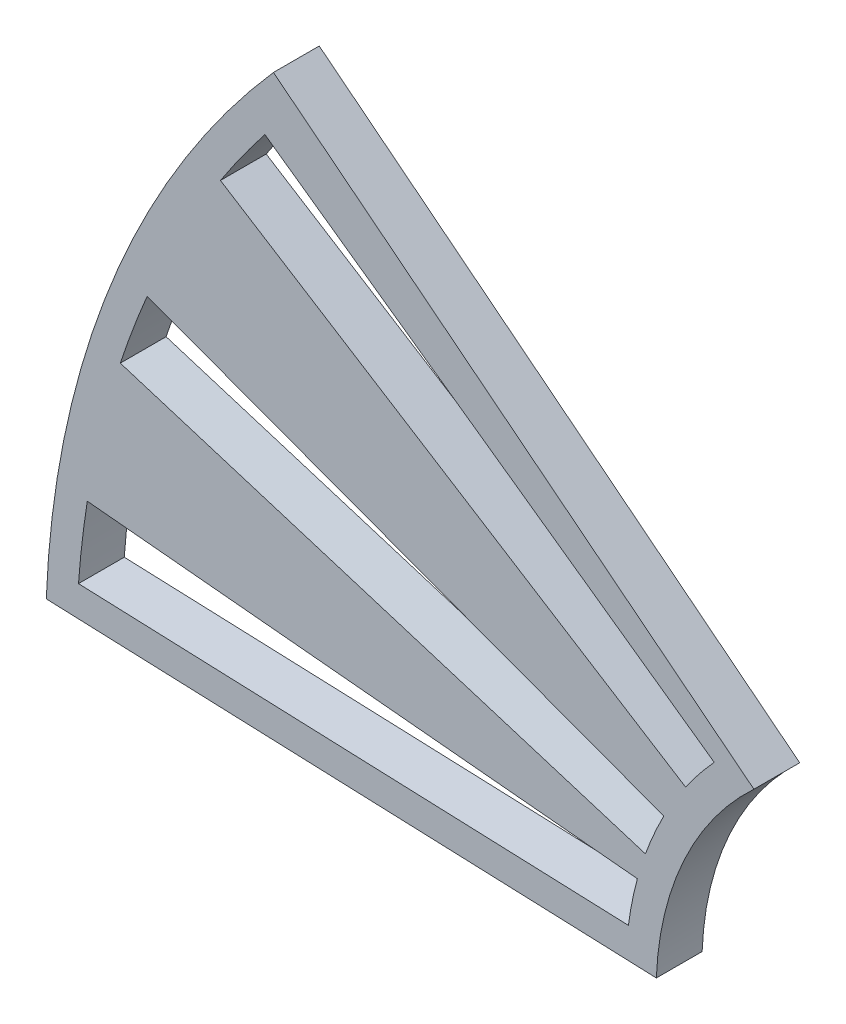
SolidWorks part; units mm, degrees
ref_plane "Front Plane" through (0, 0, 0) normal (0, 0, 1) x (1, 0, 0)
ref_plane "Top Plane" through (0, 0, 0) normal (0, 1, 0) x (1, 0, 0)
ref_plane "Right Plane" through (0, 0, 0) normal (1, 0, 0) x (0, 0, -1)
sketch "Sketch1" plane through (0, 0, 0) normal (0, 0, 1) x (1, 0, 0)
  line L0 (-19.9854, 0.7628) -> (-59.9563, 2.2884)
  line L1 (-16.3569, 14.7123) -> (-16.1915, 14.8941)
  line L2 (0, 0) -> (-50.7795, 31.96) construction
  line L3 (0, 0) -> (-57.3211, 17.7283) construction
  line L4 (-21.8167, 2.8342) -> (-57.8471, 4.2094)
  line L5 (-13.5925, 14.6712) -> (-45.0737, 39.6026)
  line L6 (-21.2283, 5.7759) -> (-57.2696, 9.1759)
  line L7 (-57.0177, 18.6812) -> (-57.0256, 18.6836)
  line L8 (-20.7005, 7.449) -> (-55.1067, 18.0901)
  line L9 (-19.4947, 10.196) -> (-53.3439, 22.7691)
  line L10 (-18.0672, 12.5529) -> (-48.5469, 31.7364)
  line L11 (-50.2398, 32.8019) -> (-50.2468, 32.8063)
  line L12 (0.5327, 0.8463) -> (-50.2468, 32.8063) construction
  line L13 (-16.1915, 14.8941) -> (-45.6332, 35.7997)
  line L15 (-16.3569, 14.7123) -> (-40.8618, 41.162) construction
  line L16 (-13.5925, 14.6712) -> (-40.7774, 44.0137) construction
  arc A0 (-45.0737, 39.6026) -> (-59.9563, 2.2884) centre (0, 0) ccw
  arc A1 (-13.5925, 14.6712) -> (-19.9854, 0.7628) centre (0, 0) ccw
  arc A2 (-45.6332, 35.7997) -> (-48.5469, 31.7364) centre (0, 0) ccw
  arc A3 (-16.3569, 14.7123) -> (-18.0672, 12.5529) centre (0, 0) ccw
  arc A4 (-53.3439, 22.7691) -> (-55.1067, 18.0901) centre (0, 0) ccw
  arc A5 (-40.8618, 41.162) -> (-57.8471, 4.2094) centre (0, 0) ccw construction
  arc A6 (-19.4947, 10.196) -> (-20.7005, 7.449) centre (0, 0) ccw
  arc A7 (-21.2283, 5.7759) -> (-21.8167, 2.8342) centre (0, 0) ccw
  arc A8 (-16.3569, 14.7123) -> (-21.8167, 2.8342) centre (0, 0) ccw construction
  arc A9 (-57.2696, 9.1759) -> (-57.8471, 4.2094) centre (0, 0) ccw
  arc A11 (-40.7774, 44.0137) -> (-59.9563, 2.2884) centre (0, 0) ccw construction
  point P16 (0.2955, 0.9554)
  dimension "D1" = 120
  dimension "D2" = 40
  dimension "D3" = 0.2459
  dimension "D4" = 15
  dimension "D5" = 2
  dimension "15" = 15
  dimension "D6" = 3
  dimension "D7" = 5
  dimension "D8" = 3
  dimension "D9" = 5
  dimension "D11" = 3
  dimension "D12" = 5
  dimension "D13" = 3
  dimension "D10" = 1
extrude "Boss-Extrude2" add sketch "Sketch1" along normal blind 3 contours L0 A0 L5 A1
extrude "Cut-Extrude1" cut sketch "Sketch1<5>" along normal through all contours A6 L9 A4 L8 | L6 A9 L4 A7 | A3 L1 L13 A2 L10 | L4 A9 L6 A7 | L8 A4 L9 A6 region at (-33.393, 24.6066, 0) region at (-41.0968, 5.6048, 0) region at (-38.6238, 15.1254, 0)
sketch "Sketch1<5>" plane through (0, 0, 0) normal (0, 0, 1) x (1, 0, 0) same geometry as "Sketch1"
ref_plane "Plane1" through (-19.9854, 0.7628, 3) normal (-0.0381, -0.9993, 0) x (-0.9993, 0.0381, 0)
